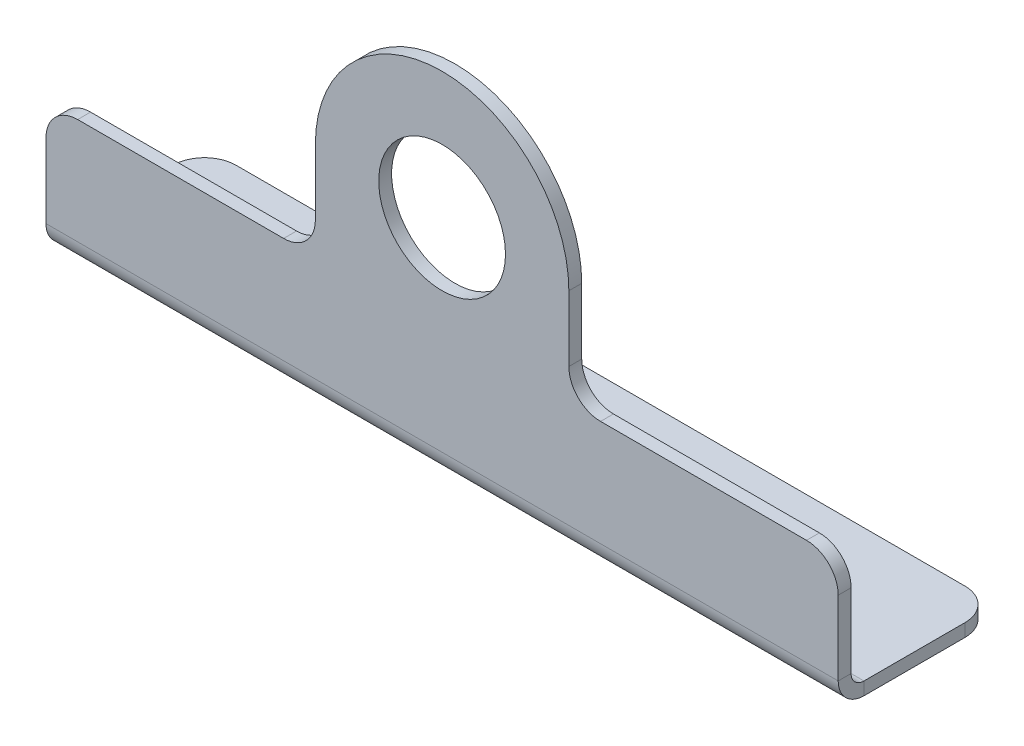
SolidWorks part; units mm, degrees
note: The reader was unsure of these and kept them because the rebuilt part matched: thickness of "Base-Flange1", "Edge-Flange1", "Sheet-Metal1", "Sheet-Metal2", "Sheet-Metal3"; flange length of "Edge-Flange1".
ref_plane "Front Plane" through (0, 0, 0) normal (0, 0, 1) x (1, 0, 0)
ref_plane "Top Plane" through (0, 0, 0) normal (0, 1, 0) x (1, 0, 0)
ref_plane "Right Plane" through (0, 0, 0) normal (1, 0, 0) x (0, 0, -1)
sketch "Sketch1" plane through (0, 0, 0) normal (0, 0, 1) x (1, 0, 0)
  line L0 (-25, 0) -> (25, 0)
  line L1 (25, 0) -> (25, 5.5)
  line L2 (23, 7.5) -> (10, 7.5)
  line L3 (8, 9.5) -> (8, 13.64)
  line L4 (-8, 13.64) -> (-8, 9.5)
  line L5 (-10, 7.5) -> (-23, 7.5)
  line L6 (-25, 5.5) -> (-25, 0)
  arc A0 (8, 13.64) -> (-8, 13.64) centre (0, 13.64) ccw
  circle A1 centre (0, 13.64) radius 4
  arc A2 (25, 5.5) -> (23, 7.5) centre (23, 5.5) ccw
  arc A3 (-23, 7.5) -> (-25, 5.5) centre (-23, 5.5) ccw
  arc A4 (10, 7.5) -> (8, 9.5) centre (10, 9.5) cw
  arc A5 (-8, 9.5) -> (-10, 7.5) centre (-10, 9.5) cw
  point P4 (0, 0)
  point P16 (25, 7.5)
  point P21 (8, 7.5)
  dimension "D1" = 8
  dimension "D3" = 8
  dimension "D6" = 2
  dimension "D2" = 13.64
  dimension "D4" = 7.5
  dimension "D5" = 50
base flange "Base-Flange1" sketch "Sketch1" thickness 0.8128 reverse thickness direction no parameters "D1"=0.8128
edge flange "Edge-Flange1" sketch "Sketch8" flange angle 90 flange length 10 flange position material outside bend radius 0.8128 thickness 0.8128 relief rectangular parameters "D6"=10
sketch "Sketch8" plane through (0, 0, -0.8128) normal (0, -1, 0) x (-1, 0, 0)
  line L0 (25, 0) -> (-25, 0) construction
  line L1 (25, 0) -> (-25, 0)
  line L2 (-25, 0) -> (-25, 9.1872)
  line L3 (-25, 9.1872) -> (25, 9.1872)
  line L4 (25, 9.1872) -> (25, 0)
  dimension "D1" = 9.1872
bend "EdgeBend1" bend radius 0.8128 bend angle 90 parameters "D5"=1
fillet "Fillet2" radius 2 2 edges at (25, -0.4064, -10) (-25, -0.4064, -10)
hole_wizard "Ø5.0mm Dowel Hole1" positions "Sketch9" profile "Sketch10" hole size "Ø5.0" standard "ANSI Metric" end condition through all
sketch "Sketch9" plane through (0, 0, 0) normal (0, 1, 0) x (1, 0, 0)
  line L2 (-23, 10) -> (23, 10) construction
  line L3 (0, 1.6256) -> (0, 10) construction
  line L4 (25, 1.6256) -> (-25, 1.6256) construction
  line L6 (0, 5.8128) -> (25, 5.8128) construction
  line L7 (25, 8) -> (25, 1.6256) construction
  line L9 (0, 5.8128) -> (-25, 5.8128) construction
  line L10 (-25, 1.6256) -> (-25, 8) construction
  point P25 (12.5, 5.8128)
  point P34 (-12.5, 5.8128)
sketch "Sketch10" plane through (-12.5, 0, -5.8128) normal (1, 0, 0) x (0, 0, 1)
  line L0 (0, 0) -> (0, 0.8128)
  line L1 (0, 0.8128) -> (2.5, 0.8128)
  line L2 (2.5, 0.8128) -> (2.5, 0)
  line L5 (2.5, 0) -> (0, 0)
  line L11 (0, -6.35) -> (0, 107.95) construction
  dimension "Thru Hole Dia." = 5
  dimension "Thru Hole Depth" = 0.8128
sketch "Sketch12" plane through (0, 0, 0) normal (0, 0, 1) x (1, 0, 0)
  point P0 (0, 13.64)
sketch "Sketch13" plane through (0, 0, 0) normal (1, 0, 0) x (0, 0, -1)
  line L0 (0, 13.64) -> (20, 13.64) construction
  dimension "D1" = 20
sketch "Bend-Lines1" [suppressed] plane through (0, 0, 0) normal (0, 1, 0) x (1, 0, 0)
sketch "Bounding-Box1" [suppressed] plane through (0, 0, 0) normal (0, 1, 0) x (1, 0, 0)
other "Bend-Notch1" [suppressed] parameters "D1"=0, "D3"=5, "D2"=1
sheet metal parameters "Sheet-Metal1" thickness 0.8128 parameters "D1"=0.7366, "D7"=3.175
flat pattern "Flat-Pattern1" [suppressed]
sketch "Bend-Lines2" plane through (0, 0, 0) normal (0, 1, 0) x (1, 0, 0)
sketch3d "Bounding-Box2" [suppressed]
  line L0 (25, 11.9999, 0) -> (-25, 11.9999, 0) construction
  line L1 (25, -19.175, 0) -> (-25, -19.175, 0) construction
  line L2 (25, 11.9999, 0) -> (25, -19.175, 0) construction
  line L3 (-25, 11.9999, 0) -> (-25, -19.175, 0) construction
sheet metal parameters "Sheet-Metal2" thickness 0.8128 parameters "D1"=0.7366, "D7"=3.175
flat pattern "Flat-Pattern1"
sketch "Bend-Lines2" plane through (0, 0, 0) normal (0, 0, 1) x (1, 0, 0)
  line L0 (-25, -1.0887) -> (25, -1.0887) construction
  line L1 (-25, -1.0887) -> (25, -1.0887) construction
sketch3d "Bounding-Box2" [suppressed]
  line L0 (-48, 23.9999, 0) -> (2, 23.9999, 0) construction
  line L1 (-48, -20.1775, 0) -> (2, -20.1775, 0) construction
  line L2 (-48, 23.9999, 0) -> (-48, -20.1775, 0) construction
  line L3 (2, 23.9999, 0) -> (2, -20.1775, 0) construction
bend of the flat pattern "Flatten-<EdgeBend1>1"
sheet metal parameters "Sheet-Metal3" thickness 0.8128 parameters "D1"=0.7366, "D7"=3.175
flat pattern "Flat-Pattern1"
sketch "Bend-Lines2" plane through (0, 0, 0) normal (0, 0, 1) x (1, 0, 0)
  line L0 (-25, -0.1448) -> (25, -0.1448) construction
  line L1 (-25, -0.1448) -> (25, -0.1448) construction
sketch3d "Bounding-Box2" [suppressed]
  line L0 (-48, 16.1399, 0) -> (2, 16.1399, 0) construction
  line L1 (-48, -14.9767, 0) -> (2, -14.9767, 0) construction
  line L2 (-48, 16.1399, 0) -> (-48, -14.9767, 0) construction
  line L3 (2, 16.1399, 0) -> (2, -14.9767, 0) construction
bend of the flat pattern "Flatten-<EdgeBend1>1"
